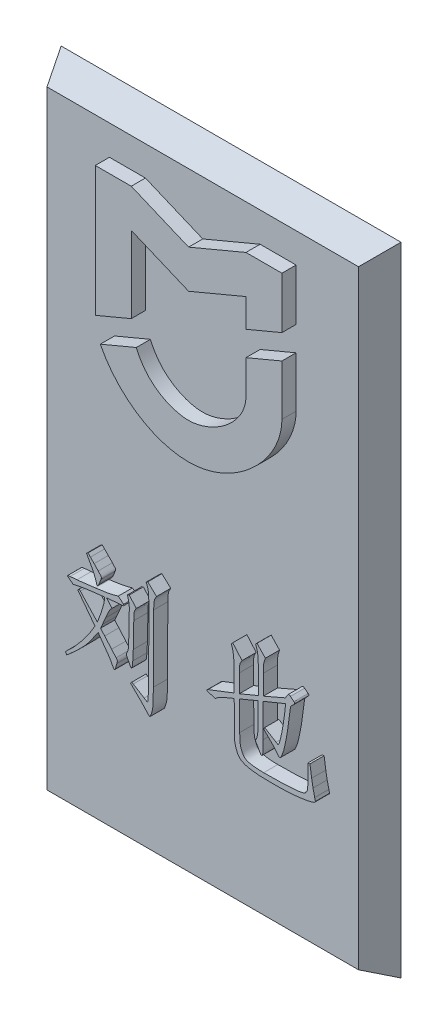
SolidWorks part; units mm, degrees
ref_plane "前视基准面" through (0, 0, 0) normal (0, 0, 1) x (1, 0, 0)
ref_plane "上视基准面" through (0, 0, 0) normal (0, 1, 0) x (1, 0, 0)
ref_plane "右视基准面" through (0, 0, 0) normal (1, 0, 0) x (0, 0, -1)
other "Configuration Table"
sketch "草图1" plane through (0, 0, 0) normal (0, 0, 1) x (1, 0, 0)
  line L18 (-12, -22.5) -> (12, -22.5)
  line L19 (-12, -22.5) -> (-12, 22.5)
  line L20 (-12, 22.5) -> (12, 22.5)
  line L21 (12, -22.5) -> (12, 22.5)
  line L22 (-12, -22.5) -> (12, 22.5) construction
  line L23 (-12, 22.5) -> (12, -22.5) construction
  point P0 (0, 0)
  dimension "D2" = 45
  dimension "D1" = 24
ref_plane "基准面1" through (0, 0, 2) normal (0, 0, 1) x (1, 0, 0)
sketch "草图2" plane through (0, 0, 2) normal (0, 0, 1) x (1, 0, 0)
  line L0 (-12, 22.5) -> (12, 22.5) construction
  line L1 (-11, -21.5) -> (11, -21.5)
  line L2 (-11, -21.5) -> (-11, 21.5)
  line L3 (-11, 21.5) -> (11, 21.5)
  line L4 (11, -21.5) -> (11, 21.5)
  line L5 (-11, -21.5) -> (11, 21.5) construction
  line L6 (-11, 21.5) -> (11, -21.5) construction
  line L7 (12, -22.5) -> (12, 22.5) construction
  point P0 (0, 0)
  dimension "D1" = 1
  dimension "D2" = 1
loft "放样1" add profiles "草图1", "草图2" connector at (-12, -22.5, 0) connector at (-11, -21.5, 2)
sketch "草图3" plane through (0, 0, 2) normal (0, 0, 1) x (1, 0, 0)
  line L0 (69.5095, 236.7647) -> (402.8428, 236.7647) construction
  line L1 (-25.2949, 7.1) -> (-27.616, 7.1) construction
  line L2 (0, 0) -> (0, 41.0504) construction
  line L3 (-6.59, 10.2338) -> (-6.59, 19.4)
  line L4 (-6.59, 19.4) -> (-4.05, 19.4)
  line L5 (-4.05, 19.4) -> (0, 17.7)
  line L6 (0, 17.7) -> (4.05, 19.4)
  line L7 (4.05, 19.4) -> (6.59, 19.4)
  line L8 (6.59, 19.4) -> (6.59, 15.7662)
  line L9 (6.59, 15.7662) -> (4.05, 14.7)
  line L10 (4.05, 14.7) -> (4.05, 16.7)
  line L11 (4.05, 16.7) -> (0, 15)
  line L12 (0, 15) -> (-4.05, 16.7)
  line L13 (-4.05, 16.7) -> (-4.05, 11.3)
  line L14 (-4.05, 11.3) -> (-6.59, 10.2338)
  line L16 (4.05, 12.9648) -> (6.59, 14.0309)
  line L17 (4.05, 14.7) -> (0, 14.7) construction
  line L18 (-4.05, 11.3) -> (0, 11.3) construction
  line L19 (11, 21.5) -> (-11, 21.5) construction
  line L20 (6.59, 14.0309) -> (6.59, 10.4595)
  line L21 (4.05, 12.9648) -> (4.05, 10.5907)
  line L22 (-3.6952, 9.7137) -> (-6.2352, 8.6475)
  line L23 (0, 7.1) -> (0, 4.56) construction
  line L24 (-23.4312, 4.56) -> (-28.3926, 4.56) construction
  spline S0 degree 3 poles (-3.6952, 9.7137) (-2.9407, 7.8881) (-0.8013, 7.0038) (2.0445, 7.2644) (4.05, 9.0403) (4.05, 10.5907) knots 0 0 0 0 0.291621 0.391621 1 1 1 1
  spline S1 degree 3 poles (-6.2352, 8.6475) (-4.8708, 5.9474) (1.073, 2.3429) (6.59, 7.9387) (6.59, 10.4595) knots 0 0 0 0 0.499283 1 1 1 1
  dimension "D9" = 1.6
  dimension "D1" = 4.05
  dimension "D2" = 6.5
  dimension "D3" = 0.3
  dimension "D4" = 2.7
  dimension "D5" = 1.7
  dimension "D6" = 2.54
  dimension "D7" = 5.4
  dimension "D8" = 7.9
extrude "凸台-拉伸2" add sketch "草图3" along normal blind 1
sketch "草图4" plane through (0, 0, 2) normal (0, 0, 1) x (1, 0, 0)
  line L6 (-11, -11) -> (11, -11) construction
  line L7 (-11, -21.5) -> (-11, 21.5) construction
  line L8 (11, -21.5) -> (11, 21.5) construction
  text T0 "刘也" font "汉仪长仿宋体" height 6
  dimension "D1" = 11
extrude "凸台-拉伸3" add sketch "草图4" along normal blind 1
sketch "草图5" plane through (0, 0, 0) normal (0, 0, -1) x (-1, 0, 0)
  line L0 (-12, -22.5) -> (-12, 22.5) construction
  line L1 (-12, 22.5) -> (12, 22.5) construction
  line L2 (12, -22.5) -> (-12, -22.5) construction
  line L3 (12, 22.5) -> (12, -22.5) construction
  circle A0 centre (-8, 14.5) radius 0.4
  circle A1 centre (8, 14.5) radius 0.4
  circle A2 centre (-8, -14.5) radius 0.4
  circle A3 centre (8, -14.5) radius 0.4
  dimension "D5" = 0.8
  dimension "D1" = 4
  dimension "D2" = 8
  dimension "D3" = 8
  dimension "D4" = 4
extrude "切除-拉伸1" cut sketch "草图5" against normal blind 1
